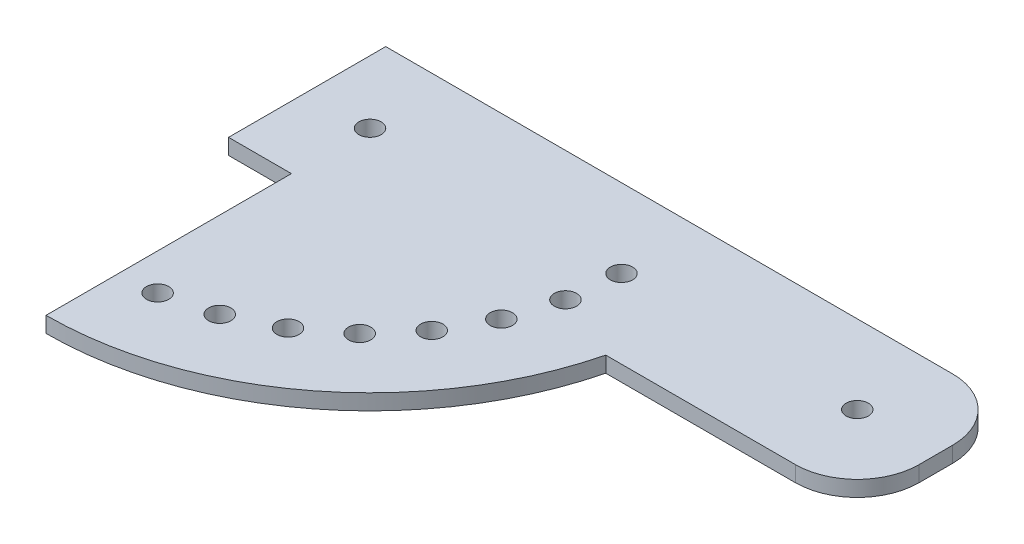
SolidWorks part; units mm, degrees
ref_plane "Front Plane" through (0, 0, 0) normal (0, 0, 1) x (1, 0, 0)
ref_plane "Top Plane" through (0, 0, 0) normal (0, 1, 0) x (1, 0, 0)
ref_plane "Right Plane" through (0, 0, 0) normal (1, 0, 0) x (0, 0, -1)
sketch "Sketch1" plane through (0, 0, 0) normal (0, 1, 0) x (1, 0, 0)
  line L0 (-12.7, -15.875) -> (-12.7, 15.875)
  line L1 (-12.7, 15.875) -> (101.8, 15.875)
  line L2 (114.3, 3.375) -> (114.3, -3.375)
  line L3 (101.8, -15.875) -> (63.5, -15.875)
  line L4 (-12.7, -15.875) -> (0, -15.875)
  line L5 (0, 0) -> (50.8, 0) construction
  line L6 (0, -65.4543) -> (0, -15.875)
  line L7 (0, 0) -> (50.8, 0) construction
  line L8 (0, 0) -> (49.7505, -10.2727) construction
  circle A0 centre (0, 0) radius 2.25
  circle A2 centre (98.425, 0) radius 2.25
  arc A4 (63.5, -15.875) -> (0, -65.4543) centre (0, 0) cw
  circle A5 centre (50.8, 0) radius 2.25
  circle A6 centre (49.7505, -10.2727) radius 2.25
  circle A7 centre (46.6454, -20.1209) radius 2.25
  circle A8 centre (41.6129, -29.1378) radius 2.25
  circle A9 centre (34.861, -36.9507) radius 2.25
  circle A10 centre (26.6687, -43.2368) radius 2.25
  circle A11 centre (17.3745, -47.7364) radius 2.25
  circle A12 centre (7.3623, -50.2637) radius 2.25
  arc A13 (114.3, -3.375) -> (101.8, -15.875) centre (101.8, -3.375) cw
  arc A14 (101.8, 15.875) -> (114.3, 3.375) centre (101.8, 3.375) cw
  point P2 (-12.7, 0)
  point P9 (45.1358, -24.1155)
  point P16 (0, 0)
  dimension "D4" = 4.5
  dimension "D5" = 4.5
  dimension "D10" = 4.5
  dimension "D9" = 12.5
  dimension "D1" = 31.75
  dimension "D2" = 12.7
  dimension "D3" = 114.3
  dimension "D6" = 15.875
  dimension "D7" = 50.8
  dimension "D8" = 12.7
  dimension "D12" = 11.667
  dimension "D11" = 8
extrude "Boss-Extrude1" add sketch "Sketch1" along normal blind 3.175
